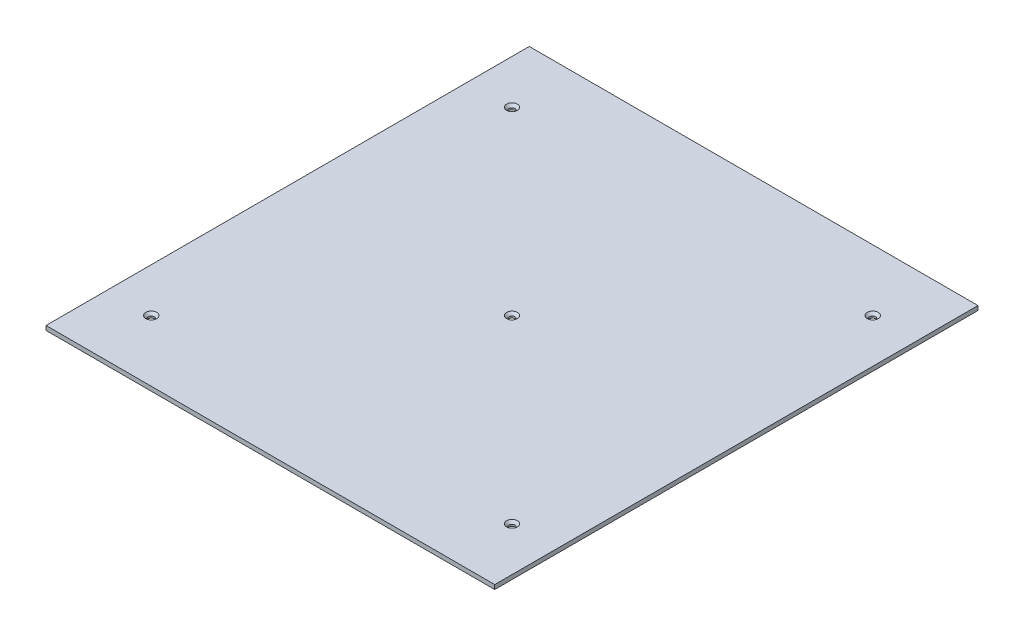
SolidWorks part; units mm, degrees
material "Copper"
ref_plane "Front Plane" through (0, 0, 0) normal (0, 0, 1) x (1, 0, 0)
ref_plane "Top Plane" through (0, 0, 0) normal (0, 1, 0) x (1, 0, 0)
ref_plane "Right Plane" through (0, 0, 0) normal (1, 0, 0) x (0, 0, -1)
sketch "Sketch1" plane through (0, 0, 0) normal (0, 1, 0) x (1, 0, 0)
  line L1 (-130, 140) -> (130, 140)
  line L2 (-130, 140) -> (-130, -140)
  line L3 (-130, -140) -> (130, -140)
  line L4 (130, 140) -> (130, -140)
  line L5 (-130, 140) -> (130, -140) construction
  line L6 (-130, -140) -> (130, 140) construction
  point P0 (0, 0)
  dimension "D1" = 260
  dimension "D2" = 280
extrude "Boss-Extrude1" add sketch "Sketch1" along normal blind 2.5
hole_wizard "CSK for M3 Flat Head Machine Screw1" positions "Sketch3" profile "Sketch2" countersink size "M3" standard "Ansi Metric" end condition through all
sketch "Sketch3" plane through (0, 2.5, 0) normal (0, 1, 0) x (-1, 0, 0)
  circle A0 centre (104.5, 104.5) radius 1.5 construction
  circle A1 centre (0, 0) radius 1.25 construction
  circle A2 centre (-104.5, 104.5) radius 1.5 construction
  circle A3 centre (-104.5, -104.5) radius 1.5 construction
  circle A4 centre (104.5, -104.5) radius 1.5 construction
  point P0 (0, 0)
  point P1 (104.5, 104.5)
  point P10 (104.5, -104.5)
  point P12 (-104.5, 104.5)
  point P14 (-104.5, -104.5)
sketch "Sketch2" plane through (0, 2.5, 0) normal (1, 0, 0) x (0, 0, 1)
  line L0 (0, 0) -> (0, 2.5)
  line L1 (0, 2.5) -> (1.7, 2.5)
  line L2 (1.7, 2.5) -> (1.7, 1.45)
  line L3 (1.7, 1.45) -> (3.15, 0)
  line L5 (3.15, 0) -> (0, 0)
  line L6 (-1.7, 1.45) -> (-3.15, 0) construction
  line L11 (0, -6.35) -> (0, 107.95) construction
  dimension "Thru Hole Dia." = 3.4
  dimension "Thru Hole Depth" = 2.5
  dimension "Near C'Sink Dia." = 6.3
  dimension "Near C'Sink Angle" = 90
